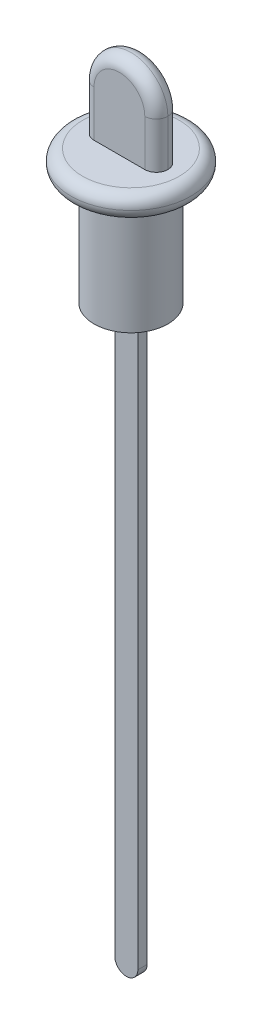
SolidWorks part; units mm, degrees
ref_plane "Front Plane" through (0, 0, 0) normal (0, 0, 1) x (1, 0, 0)
ref_plane "Top Plane" through (0, 0, 0) normal (0, 1, 0) x (1, 0, 0)
ref_plane "Right Plane" through (0, 0, 0) normal (1, 0, 0) x (0, 0, -1)
sketch "Sketch1" plane through (0, 0, 0) normal (0, 1, 0) x (1, 0, 0)
  circle A0 centre (0, 0) radius 5.08
  dimension "D1" = 10.16
extrude "Boss-Extrude1" add sketch "Sketch1" against normal blind 15.24
sketch "Sketch2" plane through (0, 0, 0) normal (0, 1, 0) x (1, 0, 0)
  circle A0 centre (0, 0) radius 8.255
  dimension "D1" = 16.51
extrude "Boss-Extrude2" add sketch "Sketch2" along normal blind 3.175
sketch "Sketch3" plane through (0, 0, 0) normal (0, 0, 1) x (1, 0, 0)
  line L0 (-5.08, 0) -> (-5.08, 3.175) construction
  line L1 (-5.08, 0) -> (-5.08, -15.24) construction
  line L2 (-8.255, 0) -> (8.255, 0) construction
  line L3 (8.255, 3.175) -> (-8.255, 3.175) construction
  line L4 (5.08, 0) -> (5.08, 3.175) construction
  line L5 (5.08, -15.24) -> (5.08, 0) construction
  line L6 (5.08, 3.175) -> (-5.08, 3.175)
  line L7 (-5.08, 3.175) -> (-5.08, 9.525)
  line L8 (5.08, 3.175) -> (5.08, 9.525)
  line L9 (5.08, 9.525) -> (-5.08, 9.525) construction
  arc A0 (-5.08, 9.525) -> (5.08, 9.525) centre (0, 9.525) cw
  dimension "D1" = 6.35
extrude "Boss-Extrude3" add sketch "Sketch3" along normal mid plane 3.175
fillet "Fillet1" radius 1.5875 8 edges at (5.08, 6.35, -1.5875) (-5.08, 6.35, -1.5875) (-5.08, 6.35, 1.5875) (0, 14.605, 1.5875) (0, 0, 8.255) (0, 3.175, 8.255) (0, 14.605, -1.5875) (5.08, 6.35, 1.5875)
sketch "Sketch4" plane through (0, -15.24, 0) normal (0, -1, 0) x (1, 0, 0)
  line L1 (1.5875, -0.635) -> (-1.5875, -0.635)
  line L2 (1.5875, -0.635) -> (1.5875, 0.635)
  line L3 (1.5875, 0.635) -> (-1.5875, 0.635)
  line L4 (-1.5875, -0.635) -> (-1.5875, 0.635)
  line L5 (1.5875, -0.635) -> (-1.5875, 0.635) construction
  line L6 (1.5875, 0.635) -> (-1.5875, -0.635) construction
  point P0 (0, 0)
  dimension "D1" = 3.175
  dimension "D2" = 1.27
extrude "Boss-Extrude4" add sketch "Sketch4" along normal blind 80.01
fillet "Fillet3" radius 1.5875 2 edges at (-1.5875, -95.25, 0) (1.5875, -95.25, 0)
